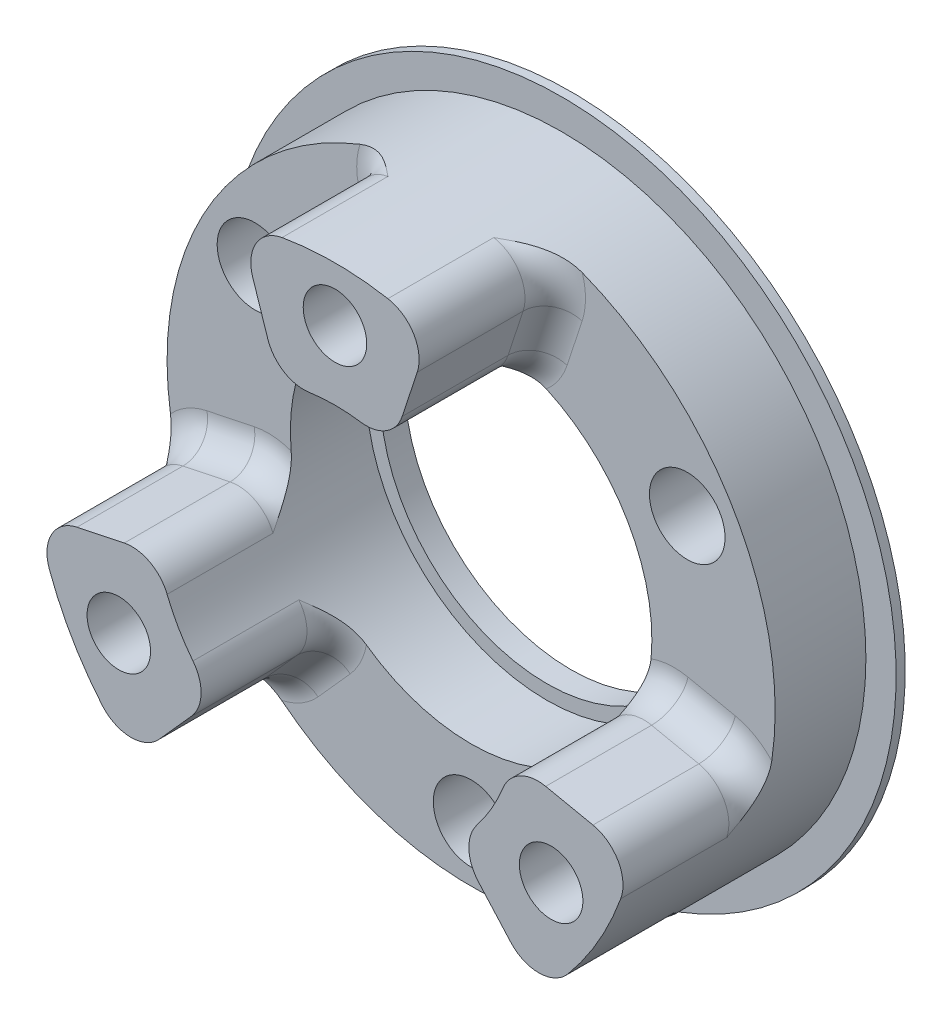
SolidWorks part; units mm, degrees
ref_plane "Front Plane" through (0, 0, 0) normal (0, 0, 1) x (1, 0, 0)
ref_plane "Top Plane" through (0, 0, 0) normal (0, 1, 0) x (1, 0, 0)
ref_plane "Right Plane" through (0, 0, 0) normal (1, 0, 0) x (0, 0, -1)
sketch "Sketch1" plane through (0, 0, 0) normal (0, 0, 1) x (1, 0, 0)
  circle A0 centre (0, 0) radius 11.95
  circle A1 centre (0, 0) radius 11
  circle A2 centre (0, 0) radius 20.1
  circle A3 centre (0, 0) radius 16.5 construction
  circle A4 centre (0, 16.5) radius 2.1
  circle A5 centre (14.2894, -8.25) radius 2.1
  circle A6 centre (-14.2894, -8.25) radius 2.1
  circle A7 centre (0, -16.5) radius 2.5
  circle A8 centre (-14.2894, 8.25) radius 2.5
  circle A9 centre (14.2894, 8.25) radius 2.5
  point P14 (0, 0)
  point P21 (0, 0)
  dimension "D1" = 23.9
  dimension "D2" = 22
  dimension "D3" = 40.2
  dimension "D4" = 33
  dimension "D5" = 4.2
  dimension "D7" = 5
  dimension "D6" = 3
  dimension "D8" = 3
extrude "Boss-Extrude1" add sketch "Sketch1" along normal blind 14.5 contours A2 A9 A8 A7 A6 A5 A4 A0 region at (-19.5315, 0, 0)
extrude "Boss-Extrude2" add sketch "Sketch1<3>" against normal blind 1 from offset 0.5 contours A0 A1 | A2 A9 A8 A7 A6 A5 A4 A0 region at (-11.612, 0, 0) region at (-19.5315, 0, 0)
sketch "Sketch1<3>" plane through (0, 0, 0) normal (0, 0, 1) x (1, 0, 0) same geometry as "Sketch1"
sketch "Sketch2" plane through (0, 0, 0) normal (0, 0, 1) x (-1, 0, 0)
  line L0 (-7.7516, 1.6208) -> (-19.6745, 4.1139)
  line L1 (0, 7.9192) -> (0, 26.8969) construction
  line L2 (7.7516, 1.6208) -> (19.6745, 4.1139)
  line L3 (19.6745, 4.1139) -> (23.7892, 4.9743) construction
  line L4 (-19.6745, 4.1139) -> (-23.7892, 4.9743) construction
  line L5 (0, 0) -> (-7.7516, 1.6208) construction
  line L6 (0, 0) -> (0, 7.9192) construction
  line L7 (0, 0) -> (7.7516, 1.6208) construction
  line L8 (0, 0) -> (-9.0322, -27.4884)
  line L9 (0, 0) -> (9.0322, -27.4884)
  circle A0 centre (0, 0) radius 11 construction
  circle A1 centre (-14.2894, -8.25) radius 2.5
  arc A2 (-9.0742, -17.9351) -> (-12.038, 2.5171) centre (-14.2894, -8.25) ccw construction
  circle A3 centre (-14.2894, -8.25) radius 2.5 construction
  circle A4 centre (0, 0) radius 20.1 construction
  arc A5 (7.7516, 1.6208) -> (-7.7516, 1.6208) centre (0, 0) ccw
  arc A6 (19.6745, 4.1139) -> (-19.6745, 4.1139) centre (0, 0) ccw
  arc A7 (-3.3416, -7.1797) -> (7.7516, 1.6208) centre (0, 0) ccw
  arc A8 (-9.0742, -17.9351) -> (19.6745, 4.1139) centre (0, 0) ccw
  arc A9 (-7.8886, 0.6959) -> (-3.3416, -7.1797) centre (0, 0) ccw
  arc A10 (-7.7516, 1.6208) -> (-7.8886, 0.6959) centre (0, 0) ccw
  arc A11 (-12.038, 2.5171) -> (-20.0694, 1.1091) centre (-14.2894, -8.25) ccw construction
  arc A12 (-19.6745, 4.1139) -> (-20.0694, 1.1091) centre (0, 0) ccw
  arc A13 (-20.0694, 1.1091) -> (-9.0742, -17.9351) centre (0, 0) ccw
  arc A14 (-20.0694, 1.1091) -> (-9.0742, -17.9351) centre (-14.2894, -8.25) ccw construction
  dimension "D1" = 22
extrude "Cut-Extrude2" cut sketch "Sketch2" against normal blind 9 from surface contours A12 A13 A8 L8 A7 A9 A10 L0 A1 region at (11.5679, 6.6787, 0) starting at face at (16.7894, 8.25, 14.5)
pattern_circular "CirPattern2" count 3 over 360 about axis through (0, 0, 14.5) along (0, 0, -1) of "Cut-Extrude2" reverse direction yes
fillet "Fillet1" radius 2.5 12 edges at (6.2745, 19.0956, 10) (-3.7304, 11.3528, 10) (-6.2745, 19.0956, 10) (3.7304, 11.3528, 10) (7.9667, -8.907, 10) (11.697, -2.4458, 10) (19.6745, -4.1139, 10) (13.4, -14.9817, 10) (-7.9667, -8.907, 10) (-13.4, -14.9817, 10) (-19.6745, -4.1139, 10) (-11.697, -2.4458, 10)
sketch "Sketch4" plane through (0, 0, -0.5) normal (0, 0, -1) x (-1, 0, 0)
  circle A0 centre (0, -16.5) radius 2.5 construction
  circle A1 centre (0, 0) radius 20.1
  circle A2 centre (0, 0) radius 20.1
  circle A3 centre (14.2894, 8.25) radius 2.5 construction
  circle A4 centre (-14.2894, 8.25) radius 2.5 construction
  circle A5 centre (0, -16.5) radius 2.5
  circle A6 centre (14.2894, 8.25) radius 2.5
  circle A7 centre (-14.2894, 8.25) radius 2.5
  circle M4 centre (-14.2894, 8.25) radius 2.5
  circle M5 centre (14.2894, 8.25) radius 2.5
  circle M6 centre (0, -16.5) radius 2.5
  dimension "D1" = 0
extrude "Boss-Extrude3" add sketch "Sketch4" against normal blind 2 contours M4 | M5 | M6 region at (0, -16.5, -0.5) region at (-14.2894, 8.25, -0.5) region at (14.2894, 8.25, -0.5)
sketch "Sketch5" plane through (0, 0, -0.5) normal (0, 0, -1) x (-1, 0, 0)
  circle A0 centre (0, 0) radius 11
  circle A1 centre (0, 0) radius 22.1
  circle A2 centre (14.2894, -8.25) radius 2.1 construction
  circle A3 centre (-14.2894, -8.25) radius 2.1 construction
  circle A4 centre (0, 16.5) radius 2.1 construction
  circle A5 centre (14.2894, -8.25) radius 2.1
  circle A6 centre (-14.2894, -8.25) radius 2.1
  circle A7 centre (0, 16.5) radius 2.1
  dimension "D1" = 44.2
extrude "Boss-Extrude4" add sketch "Sketch5" along normal blind 0.6
fillet "Fillet2" radius 2 18 edges at (18.7253, -4.7967, 5.5) (12.2374, -3.1569, 5.5) (13.5167, -13.8183, 5.5) (8.8527, -9.0195, 5.5) (15.4918, -3.2393, 5.5) (10.5512, -11.7966, 5.5) (-13.5167, -13.8183, 5.5) (-8.8527, -9.0195, 5.5) (-18.7253, -4.7967, 5.5) (-12.2374, -3.1569, 5.5) (-5.2086, 18.615, 5.5) (-3.3848, 12.1764, 5.5) (5.2086, 18.615, 5.5) (3.3848, 12.1764, 5.5) (-10.5512, -11.7966, 5.5) (-15.4918, -3.2393, 5.5) (-4.9406, 15.0359, 5.5) (4.9406, 15.0359, 5.5)
